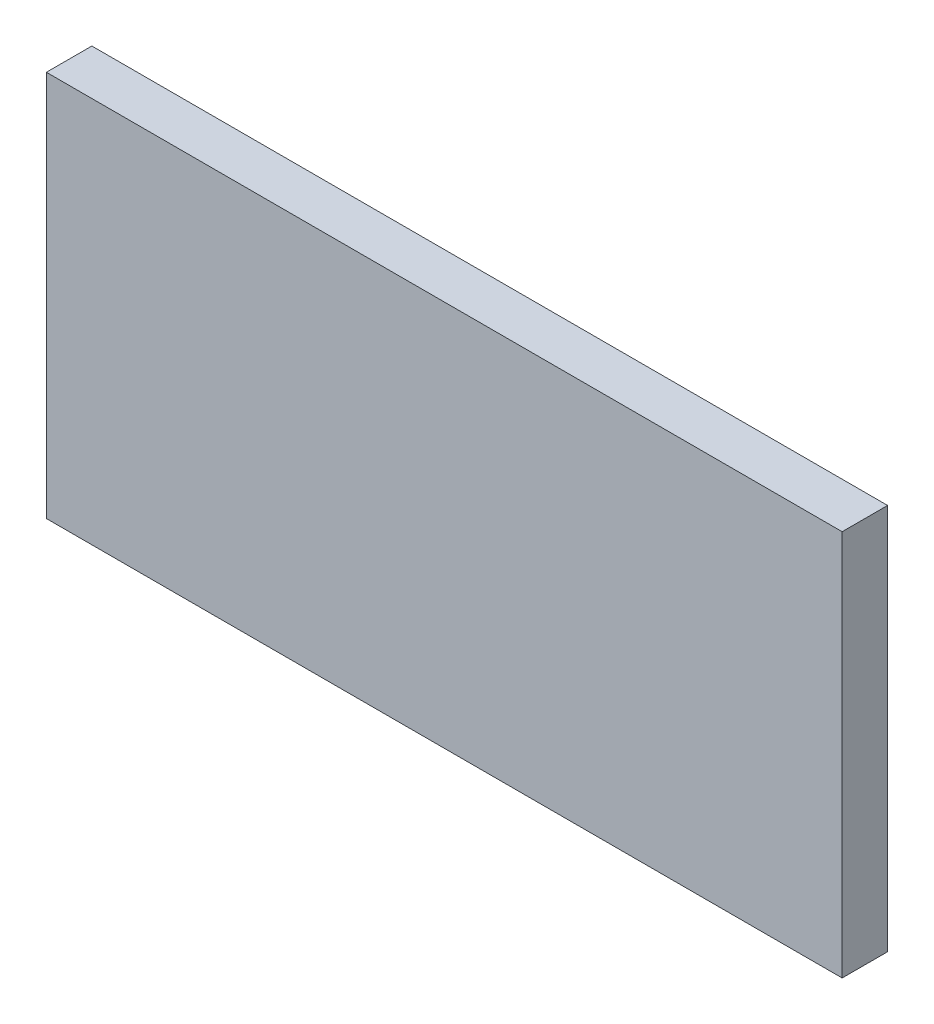
SolidWorks part; units mm, degrees
material "Клен"
ref_plane "Спереди" through (0, 0, 0) normal (0, 0, 1) x (1, 0, 0)
ref_plane "Сверху" through (0, 0, 0) normal (0, 1, 0) x (1, 0, 0)
ref_plane "Справа" through (0, 0, 0) normal (1, 0, 0) x (0, 0, -1)
sketch "Эскиз1" plane through (0, 0, 0) normal (0, 0, 1) x (1, 0, 0)
  line L0 (0, 0) -> (0, -200) construction
  line L1 (0, 0) -> (350, 0)
  line L2 (0, 0) -> (0, 170)
  line L3 (0, 170) -> (350, 170)
  line L4 (350, 0) -> (350, 170)
  line L5 (300, -200) -> (80, -200) construction
  dimension "D1" = 350
  dimension "D2" = 200
  dimension "D3" = 170
extrude "Бобышка-Вытянуть1" add sketch "Эскиз1" along normal blind 20
